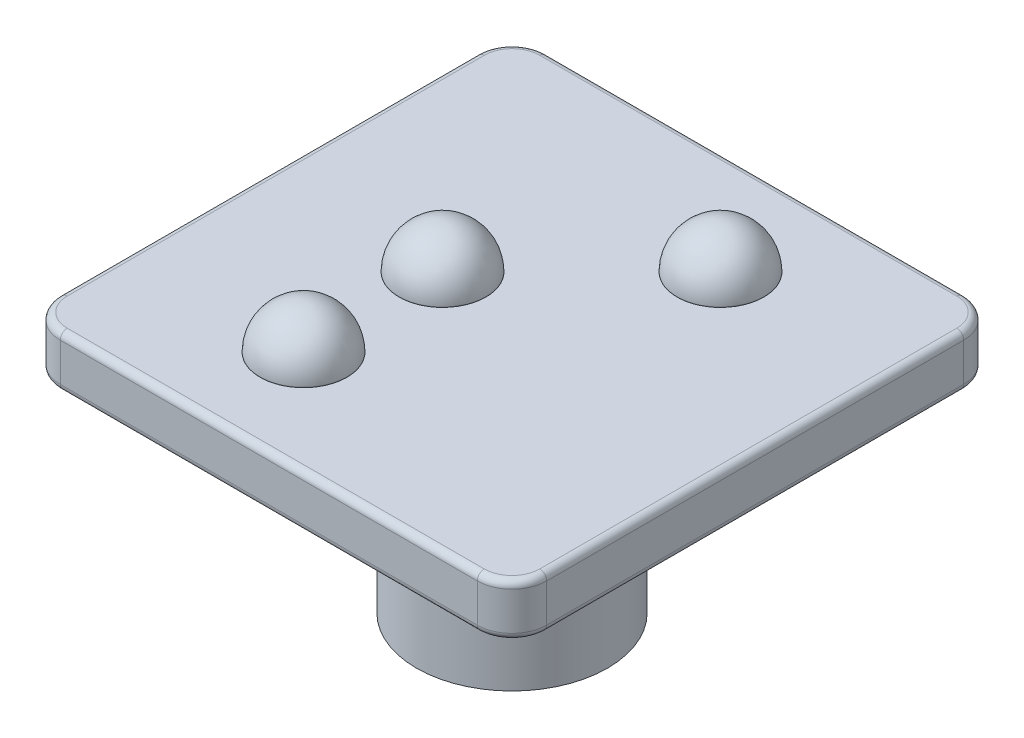
SolidWorks part; units mm, degrees
ref_plane "Front Plane" through (0, 0, 0) normal (0, 0, 1) x (1, 0, 0)
ref_plane "Top Plane" through (0, 0, 0) normal (0, 1, 0) x (1, 0, 0)
ref_plane "Right Plane" through (0, 0, 0) normal (1, 0, 0) x (0, 0, -1)
sketch "Sketch1" plane through (0, 0, 0) normal (0, 1, 0) x (1, 0, 0)
  line L1 (-7.3247, 4.3967) -> (4.6753, 4.3967)
  line L2 (-8.3247, 3.3967) -> (-8.3247, -8.6033)
  line L3 (-7.3247, -9.6033) -> (4.6753, -9.6033)
  line L4 (5.6753, 3.3967) -> (5.6753, -8.6033)
  arc A0 (-8.3247, -8.6033) -> (-7.3247, -9.6033) centre (-7.3247, -8.6033) ccw
  arc A1 (4.6753, -9.6033) -> (5.6753, -8.6033) centre (4.6753, -8.6033) ccw
  arc A2 (4.6753, 4.3967) -> (5.6753, 3.3967) centre (4.6753, 3.3967) cw
  arc A3 (-7.3247, 4.3967) -> (-8.3247, 3.3967) centre (-7.3247, 3.3967) ccw
  point P8 (5.6753, -9.6033)
  point P11 (5.6753, 4.3967)
  point P14 (-8.3247, 4.3967)
  dimension "D3" = 1
  dimension "D1" = 14
  dimension "D2" = 14
extrude "Boss-Extrude1" add sketch "Sketch1" along normal blind 1.5
sketch "Sketch2" plane through (0, 0, 0) normal (0, -1, 0) x (1, 0, 0)
  line L0 (-7.3247, 9.6033) -> (4.6753, 9.6033) construction
  line L1 (5.6753, 8.6033) -> (5.6753, -3.3967) construction
  line L2 (-1.3247, -4.3967) -> (-1.3247, 9.6033) construction
  line L3 (-8.3247, 2.6033) -> (5.6753, 2.6033) construction
  line L4 (-8.3247, -3.3967) -> (-8.3247, 8.6033) construction
  circle A0 centre (-1.3247, 2.6033) radius 2.75
  dimension "D1" = 7
  dimension "D2" = 7
extrude "Boss-Extrude2" add sketch "Sketch2" along normal blind 6
sketch "Sketch3" plane through (0, -6, 0) normal (0, -1, 0) x (1, 0, 0)
  line L0 (-1.3247, 5.3533) -> (-1.3247, -0.1467) construction
  line L1 (-3.3247, 3.1533) -> (0.6753, 3.1533)
  line L2 (-3.3247, 3.1533) -> (-3.3247, 2.0533)
  line L3 (-3.3247, 2.0533) -> (0.6753, 2.0533)
  line L4 (0.6753, 3.1533) -> (0.6753, 2.0533)
  line L5 (-1.8747, 4.6033) -> (-0.7747, 4.6033)
  line L6 (-1.8747, 4.6033) -> (-1.8747, 0.6033)
  line L7 (-1.8747, 0.6033) -> (-0.7747, 0.6033)
  line L8 (-0.7747, 4.6033) -> (-0.7747, 0.6033)
  line L9 (-4.0747, 2.6033) -> (1.4253, 2.6033) construction
  circle A3 centre (-1.3247, 2.6033) radius 2.75 construction
  circle A4 centre (-1.3247, 2.6033) radius 2.75 construction
  dimension "D7" = 0.55
  dimension "D1" = 4
  dimension "D2" = 1.1
  dimension "D3" = 1.1
  dimension "D4" = 4
  dimension "D8" = 0.55
extrude "Cut-Extrude1" cut sketch "Sketch3" against normal blind 6 contours L8 L5 L6 L1 | L1 L8 L3 L4 | L8 L1 L6 L3 | L6 L1 L2 L3 | L8 L3 L6 L7 region at (-2.5997, -6, 2.6033) region at (-1.3247, -6, 3.8783) region at (-1.3247, -6, 2.6033) region at (-0.0497, -6, 2.6033) region at (-1.3247, -6, 1.3283)
chamfer "Chamfer1" distance 0.3 angle 45 12 edges at (-1.3247, -6, 0.6033) (-1.8747, -6, 1.3283) (-2.5997, -6, 2.0533) (-3.3247, -6, 2.6033) (-2.5997, -6, 3.1533) (-0.7747, -6, 1.3283) (-0.0497, -6, 2.0533) (0.6753, -6, 2.6033) (-0.0497, -6, 3.1533) (-0.7747, -6, 3.8783) (-1.3247, -6, 4.6033) (-1.8747, -6, 3.8783)
fillet "Fillet1" radius 1 1 edges at (-1.3247, 0, -0.1467)
sketch "Sketch4" plane through (0, 1.5, 0) normal (0, 1, 0) x (1, 0, 0)
  line L0 (-1.3247, 4.3967) -> (-1.3247, -9.6033) construction
  line L1 (4.6753, 4.3967) -> (-7.3247, 4.3967) construction
  line L2 (-7.3247, -9.6033) -> (4.6753, -9.6033) construction
  line L3 (5.6753, -2.6033) -> (-8.3247, -2.6033) construction
  line L4 (-8.3247, 3.3967) -> (-8.3247, -8.6033) construction
  line L5 (5.6753, -8.6033) -> (5.6753, 3.3967) construction
  line L6 (-3.3247, 4.3967) -> (-3.3247, -9.6033) construction
  line L7 (0.6753, 4.3967) -> (0.6753, -9.6033) construction
  line L8 (-8.3247, 1.3967) -> (5.6753, 1.3967) construction
  line L9 (5.6753, -6.6033) -> (-8.3247, -6.6033) construction
  circle A2 centre (-3.3247, -2.6033) radius 1.25
  circle A3 centre (-3.3247, -6.6033) radius 1.25
  circle A5 centre (0.6753, 1.3967) radius 1.25
  dimension "D1" = 4
  dimension "D2" = 4
  dimension "D3" = 2
  dimension "D4" = 2
extrude "Boss-Extrude3" add sketch "Sketch4" along normal blind 0.01
dome "Dome2" faces to dome 1 distance 1.25 reverse direction no elliptical dome no face at (0.6753, 1.51, -0.1467) parameters "D1"=1.25
dome "Dome3" faces to dome 1 distance 1.25 reverse direction no elliptical dome no face at (-3.3247, 1.51, 3.8533) parameters "D1"=1.25
dome "Dome5" faces to dome 1 distance 1.25 reverse direction no elliptical dome no face at (-3.3247, 1.51, 7.8533) parameters "D1"=1.25
fillet "Fillet3" radius 0.2 16 edges at (5.3824, 1.5, -4.1038) (5.6753, 1.5, 2.6033) (5.3824, 1.5, 9.3104) (-1.3247, 1.5, 9.6033) (-8.0318, 1.5, 9.3104) (-8.0318, 1.5, -4.1038) (-8.3247, 1.5, 2.6033) (-1.3247, 1.5, -4.3967) (5.3824, 0, 9.3104) (5.6753, 0, 2.6033) (5.3824, 0, -4.1038) (-1.3247, 0, -4.3967) (-8.0318, 0, -4.1038) (-8.3247, 0, 2.6033) (-8.0318, 0, 9.3104) (-1.3247, 0, 9.6033)
